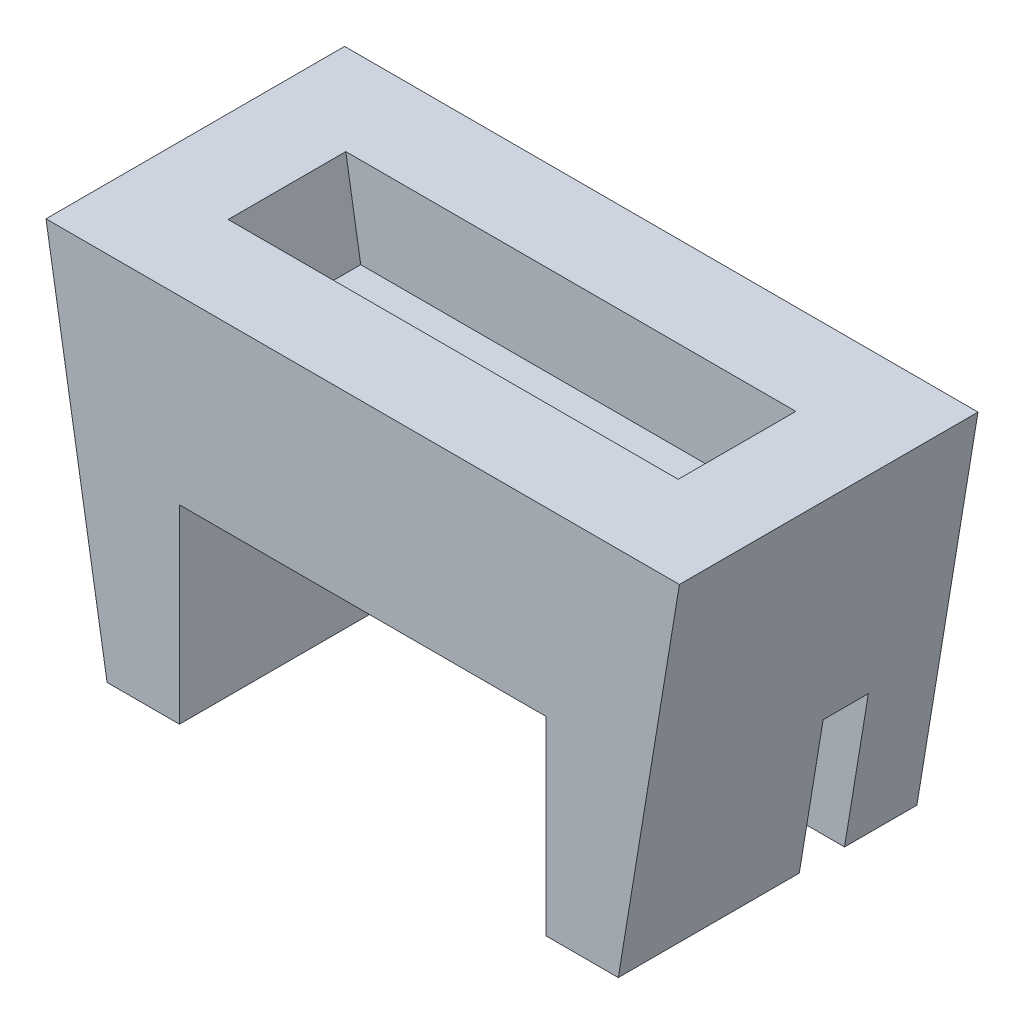
SolidWorks part; units mm, degrees
ref_plane "Plano frontal" through (0, 0, 0) normal (0, 0, 1) x (1, 0, 0)
ref_plane "Plano superior" through (0, 0, 0) normal (0, 1, 0) x (1, 0, 0)
ref_plane "Plano direito" through (0, 0, 0) normal (1, 0, 0) x (0, 0, -1)
sketch "Esboço1" plane through (0, 0, 0) normal (0, 0, 1) x (1, 0, 0)
  line L0 (-35, 20) -> (35, 20)
  line L1 (-35, 20) -> (-28.25, -21)
  line L2 (-28.25, -21) -> (-20.25, -21)
  line L3 (-20.25, -21) -> (-20.25, 0)
  line L4 (-20.25, 0) -> (20.25, 0)
  line L5 (20.25, 0) -> (20.25, -21)
  line L6 (20.25, -21) -> (28.25, -21)
  line L7 (28.25, -21) -> (35, 20)
  point P2 (0, 20)
  point P9 (-40.9642, 17.7527)
  point P11 (0, 0)
  point P12 (-27.02, -21)
  point P13 (27.2206, -21)
  dimension "D1" = 40.5
  dimension "D2" = 21
  dimension "D3" = 70
  dimension "D4" = 20
  dimension "D5" = 8
extrude "Ressalto-extrusão1" add sketch "Esboço1" along normal blind 30
sketch "Esboço2" plane through (0, 0, 0) normal (0, 0, -1) x (-1, 0, 0)
  line L0 (-35, 20) -> (35, 20)
  line L1 (35, 20) -> (28.25, -21)
  line L2 (28.25, -21) -> (-28.25, -21)
  line L3 (-28.25, -21) -> (-35, 20)
extrude "Ressalto-extrusão2" add sketch "Esboço2" along normal blind 3
shell "Casca1" thickness 10 removed face at (0, 20, 13.5)
sketch "Esboço3" plane through (20.25, 0, 0) normal (-1, 0, 0) x (0, 0, 1)
  line L0 (5, -25) -> (5, -5)
  line L1 (5, -5) -> (10, -5)
  line L2 (10, -5) -> (10, -25)
  line L3 (10, -25) -> (5, -25)
  line L4 (30, 0) -> (30, -21) construction
  line L6 (30, 0) -> (0, 0) construction
  dimension "D1" = 20
  dimension "D2" = 5
  dimension "D3" = 5
  dimension "D4" = 20
extrude "Corte-extrusão1" cut sketch "Esboço3" against normal through all
